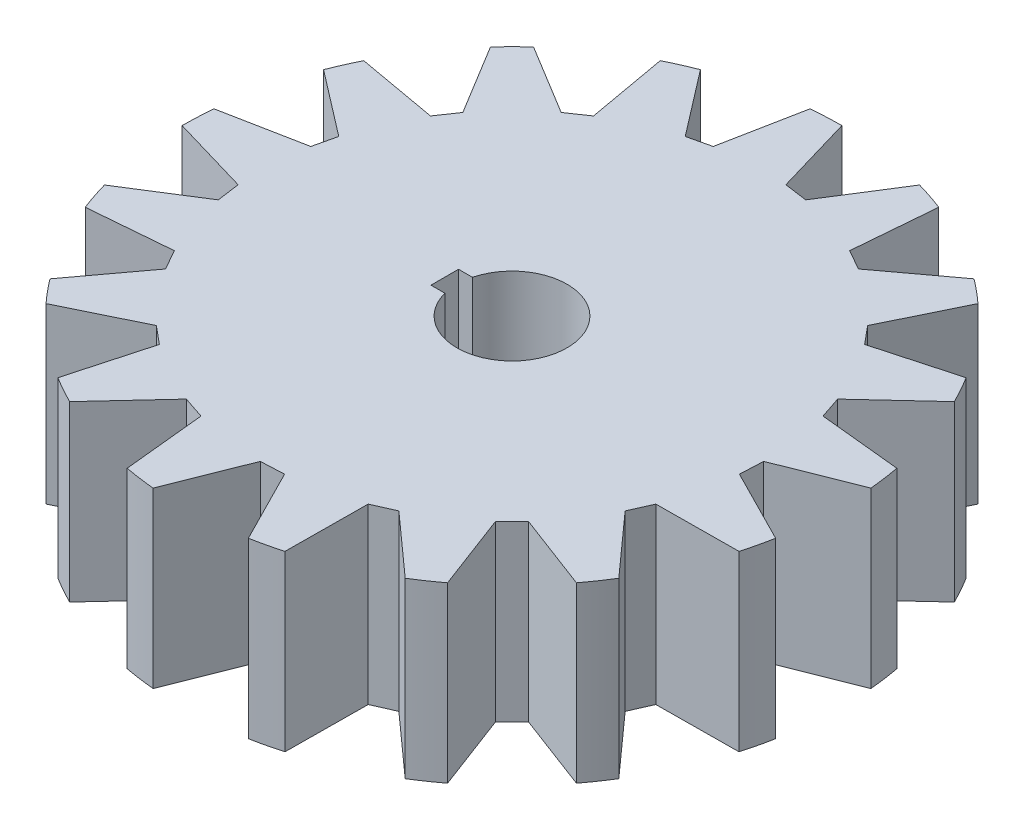
SolidWorks part; units mm, degrees
note: '?' marks a value the reader was unsure of.
ref_plane "Plan de face" through (0, 0, 0) normal (0, 0, 1) x (1, 0, 0)
ref_plane "Plan de dessus" through (0, 0, 0) normal (0, 1, 0) x (1, 0, 0)
ref_plane "Plan de droite" through (0, 0, 0) normal (1, 0, 0) x (0, 0, -1)
sketch "Esquisse1" plane through (0, 0, 0) normal (0, 0, 1) x (1, 0, 0)
  line L0 (-76, 40) -> (-76, 0)
  line L1 (-50, 40) -> (0, 40)
  line L2 (0, 40) -> (0, 0)
  line L3 (0, 40) -> (0, 0) construction
  line L4 (0, 0) -> (-50, 0)
  line L18 (-76, 40) -> (-50, 40)
  line L19 (-50, 40) -> (-50, 0) construction
  line L20 (-50, 0) -> (-76, 0)
  dimension "D2" = 40
  dimension "D3" = 76
  dimension "D15" = 50
revolve "Révolution1" add sketch "Esquisse1" angle 360 about L3
sketch "Esquisse5" plane through (0, 40, 0) normal (0, 1, 0) x (1, 0, 0)
  line L0 (0, 0) -> (0, 76) construction
  line L1 (0, 0) -> (-27.4544, 70.8679) construction
  line L2 (-27.4544, 70.8679) -> (-15.8725, 55.7859)
  line L3 (-15.8725, 55.7859) -> (-10.6575, 57.0124)
  line L4 (-10.6575, 57.0124) -> (-7.0124, 75.6758)
  line L5 (-7.0124, 75.6758) -> (0, 76)
  line L6 (-7.0124, 75.6758) -> (0, 0) construction
  line L7 (-10.6575, 57.0124) -> (0, 0) construction
  line L8 (-15.8725, 55.7859) -> (0, 0) construction
  line L9 (0, 76) -> (0, 108.0563)
  line L10 (0, 108.0563) -> (-38.2804, 98.3017)
  line L11 (-38.2804, 98.3017) -> (-27.4544, 70.8679)
  circle A0 centre (0, 0) radius 76 construction
  circle A1 centre (0, 0) radius 58 construction
  circle A2 centre (0, 0) radius 76 construction
  dimension "D1" = 21.176
  dimension "D2" = 5.294
  dimension "D3" = 5.294
  dimension "D5" = 116
  dimension "D4" = 5.294
extrude "Enlèv. mat.-Extru.3" cut sketch "Esquisse5" against normal through all
ref_axis "Axe1" through (0, 39.3, 0) along (0, -1, 0)?
pattern_circular "Répétition circulaire1" count 17 over 360 about axis through (0, 0, 0) along (0, 1, 0) of "Enlèv. mat.-Extru.3"
sketch "Esquisse6" plane through (0, 40, 0) normal (0, 1, 0) x (1, 0, 0)
  line L0 (0, 0) -> (-12.7, 0) construction
  line L1 (-12.2967, 3.175) -> (-15.4967, 3.175)
  line L2 (-15.4967, 3.175) -> (-15.4967, -3.175)
  line L3 (-15.4967, -3.175) -> (-12.2967, -3.175)
  line L4 (-12.7, 0) -> (-15.4967, 0) construction
  circle A0 centre (0, 0) radius 12.7 construction
  arc A1 (-12.2967, 3.175) -> (-12.2967, -3.175) centre (0, 0) cw
  dimension "D3" = 25.4
  dimension "D1" = 6.35
  dimension "D2" = 3.2
extrude "Enlèv. mat.-Extru.4" cut sketch "Esquisse6" against normal through all
